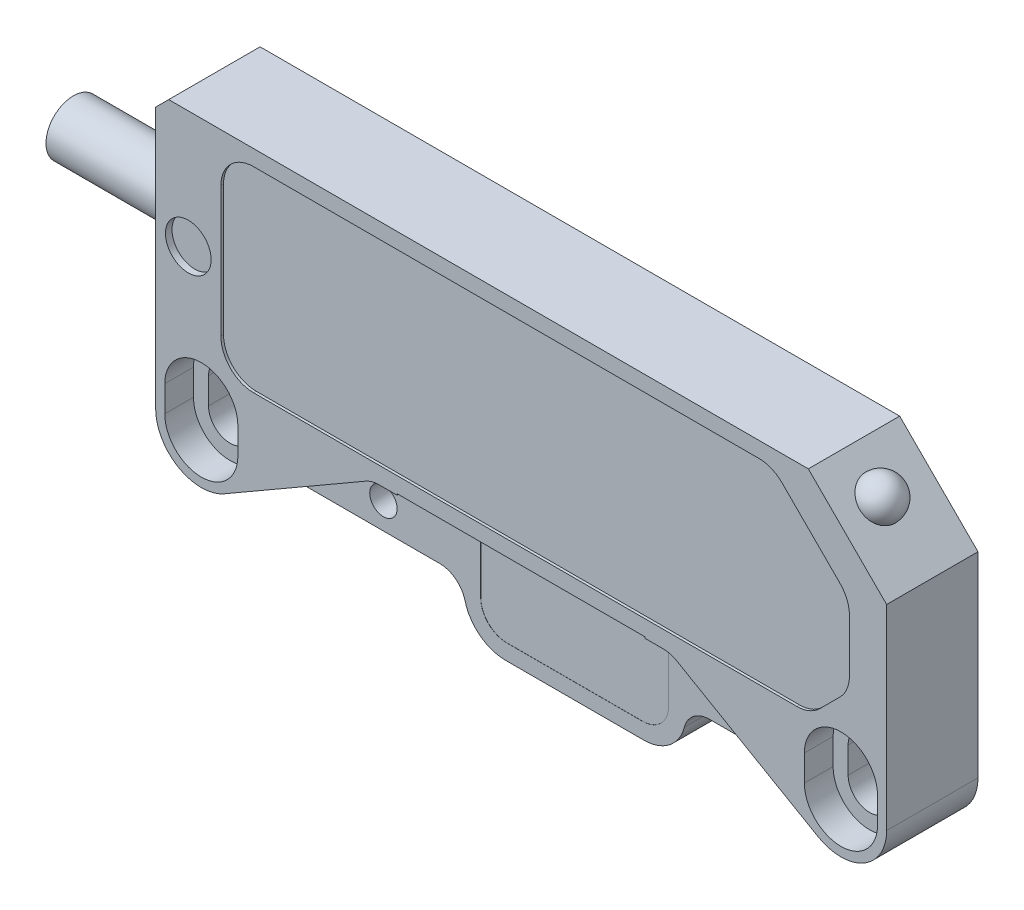
SolidWorks part; units mm, degrees
material "Zinc AG40A (Zn-4Al-0.4Mg; Zamak 3), Cast"
ref_plane "Front Plane" through (0, 0, 0) normal (0, 0, 1) x (1, 0, 0)
ref_plane "Top Plane" through (0, 0, 0) normal (0, 1, 0) x (1, 0, 0)
ref_plane "Right Plane" through (0, 0, 0) normal (1, 0, 0) x (0, 0, -1)
sketch "Sketch1" plane through (0, 0, 0) normal (0, 0, 1) x (1, 0, 0)
  line L1 (28, 0) -> (28, -11.4) construction
  line L2 (0, -4) -> (0, 17)
  line L3 (0, 17) -> (56, 17)
  line L4 (56, -4) -> (56, 17)
  line L5 (28, 17) -> (28, 0) construction
  line L7 (-0.3, 0) -> (16.888, 0) construction
  line L8 (3.5, -7.5) -> (19.5, -7.5)
  line L9 (52.5, -7.5) -> (36.5, -7.5)
  line L10 (19.5, -7.5) -> (19.5, -11.4)
  line L11 (19.5, -11.4) -> (36.5, -11.4)
  line L12 (36.5, -7.5) -> (36.5, -11.4)
  arc A0 (3.5, -7.5) -> (0, -4) centre (3.5, -4) cw
  arc A1 (52.5, -7.5) -> (56, -4) centre (52.5, -4) ccw
  dimension "D4" = 3.5
  dimension "D6" = 21
  dimension "D2" = 56
  dimension "D3" = 11.4
  dimension "D5" = 17
  dimension "D7" = 17
extrude "Boss-Extrude1" add sketch "Sketch1" along normal blind 7
sketch "Sketch2" plane through (0, 0, 7) normal (0, 0, 1) x (1, 0, 0)
  line L0 (0, 17) -> (0, -4) construction
  line L1 (5, 15.8) -> (5, 0.8)
  line L2 (5, 15.8) -> (47.25, 15.8)
  line L3 (47.25, 15.8) -> (53.15, 9.9)
  line L4 (5, 0.8) -> (50.15, 0.8)
  line L5 (28, -11.4) -> (28, 15.8) construction
  line L6 (56, 17) -> (0, 17) construction
  line L7 (53.15, 9.9) -> (53.15, 3.8)
  line L8 (19.5, -11.4) -> (36.5, -11.4) construction
  line L9 (53.15, 3.8) -> (50.15, 0.8)
  point P9 (53.15, 0.8)
  dimension "D1" = 45
  dimension "D2" = 15
  dimension "D3" = 5.9
  dimension "D4" = 1.2
  dimension "D5" = 48.15
  dimension "D8" = 3
  dimension "D6" = 5
extrude "Cut-Extrude1" cut sketch "Sketch2" against normal blind 0.2
fillet "Fillet1" radius 2.5 6 edges at (5, 0.8, 6.9) (5, 15.8, 6.9) (53.15, 9.9, 6.9) (47.25, 15.8, 6.9) (50.15, 0.8, 6.9) (53.15, 3.8, 6.9)
chamfer "Chamfer1" distance 6 angle 45 1 edges at (56, 17, 3.5)
sketch "Sketch6" plane through (0, 0, 7) normal (0, 0, 1) x (1, 0, 0)
  line L0 (49.7, -4) -> (49.7, -2)
  line L1 (55.3, -4) -> (55.3, -2)
  line L2 (56, -4) -> (56, 11) construction
  line L4 (50, 17) -> (0, 17) construction
  arc A0 (49.7, -4) -> (55.3, -4) centre (52.5, -4) ccw
  arc A4 (55.3, -2) -> (49.7, -2) centre (52.5, -2) ccw
  dimension "D1" = 5.6
  dimension "D4" = 21
  dimension "D2" = 2
  dimension "D3" = 0.7
extrude "Cut-Extrude4" cut sketch "Sketch6" against normal blind 2.2
ref_plane "Plane1" through (0, 0, 3.5) normal (0, 0, 1) x (1, 0, 0)
sketch "Sketch9" plane through (0, 0, 4.8) normal (0, 0, 1) x (1, 0, 0)
  line L4 (54.15, -4) -> (54.15, -2)
  line L5 (50.85, -2) -> (50.85, -4)
  line L6 (54.15, -4) -> (54.15, -2)
  line L7 (50.85, -2) -> (50.85, -4)
  arc A4 (50.85, -4) -> (54.15, -4) centre (52.5, -4) ccw
  arc A5 (54.15, -2) -> (50.85, -2) centre (52.5, -2) ccw
  arc A6 (50.85, -4) -> (54.15, -4) centre (52.5, -4) ccw
  arc A7 (54.15, -2) -> (50.85, -2) centre (52.5, -2) ccw
  dimension "D1" = 1.15
extrude "Cut-Extrude5" cut sketch "Sketch9" against normal through all
mirror "Mirror1" about plane through (0, 0, 3.5) normal (0, 0, 1) of "Cut-Extrude4"
sketch "Sketch14" plane through (0, 24, 0) normal (1, 0, 0) x (0, -1, 0)
  line L0 (7, -7) -> (7, 0) construction
  line L2 (7, 0) -> (28, 0) construction
  circle A0 centre (16, -3.5) radius 2.2
  dimension "D1" = 4.4
  dimension "D2" = 9
  dimension "D3" = 3.5
extrude "Cut-Extrude9" cut sketch "Sketch14" along normal blind 0.2
sketch "Sketch19" plane through (0, 0, 7) normal (0, 0, 1) x (1, 0, 0)
  line L0 (19.5, -11.4) -> (36.5, -11.4) construction
  line L1 (20.8, -0.4) -> (35.2, -0.4)
  line L2 (20.8, -0.4) -> (20.8, -8.2)
  line L3 (22.8, -10.2) -> (33.2, -10.2)
  line L4 (35.2, -0.4) -> (35.2, -8.2)
  line L5 (28, -11.4) -> (28, 20.6935) construction
  arc A1 (20.8, -8.2) -> (22.8, -10.2) centre (22.8, -8.2) ccw
  arc A2 (33.2, -10.2) -> (35.2, -8.2) centre (33.2, -8.2) ccw
  dimension "D2" = 9.8
  dimension "D4" = 2
  dimension "D1" = 14.4
  dimension "D3" = 1.2
extrude "Cut-Extrude10" cut sketch "Sketch19" against normal blind 4.11
chamfer "Chamfer3" distance 1 angle 45 1 edges at (0, 17, 3.5)
fillet "Fillet3" radius 3.2 2 edges at (36.5, -11.4, 3.5) (19.5, -11.4, 3.5)
sketch "Sketch28" plane through (0, 0, 7) normal (0, 0, 1) x (1, 0, 0)
  line L0 (16.0981, -0.7679) -> (5.25, -7.0311)
  line L1 (0, 16) -> (0, -4) construction
  line L2 (3.5, -7.5) -> (16.6824, -7.5)
  line L3 (28, -15.8188) -> (28, 23.915) construction
  line L4 (17.6824, -8.5) -> (17.6824, -14.5773)
  line L5 (17.6824, -14.5773) -> (38.3176, -14.5773)
  line L6 (3.5, -7.5) -> (19.5, -7.5) construction
  line L7 (17.0981, -0.5) -> (18.5, -0.5)
  line L8 (18.5, -0.4) -> (37.5, -0.4)
  line L9 (37.5, -0.5) -> (37.5, -0.4)
  line L10 (38.9019, -0.5) -> (37.5, -0.5)
  line L11 (38.3176, -8.5) -> (38.3176, -14.5773)
  line L12 (18.5, -0.5) -> (18.5, -0.4)
  line L13 (52.5, -7.5) -> (39.3176, -7.5)
  line L14 (39.9019, -0.7679) -> (50.75, -7.0311)
  arc A0 (5.25, -7.0311) -> (3.5, -7.5) centre (3.5, -4) cw
  arc A1 (16.0981, -0.7679) -> (17.0981, -0.5) centre (17.0981, -2.5) cw
  arc A2 (38.3176, -8.5) -> (39.3176, -7.5) centre (39.3176, -8.5) cw
  arc A3 (0, -4) -> (3.5, -7.5) centre (3.5, -4) ccw construction
  arc A4 (39.9019, -0.7679) -> (38.9019, -0.5) centre (38.9019, -2.5) ccw
  arc A5 (50.75, -7.0311) -> (52.5, -7.5) centre (52.5, -4) ccw
  arc A6 (17.6824, -8.5) -> (16.6824, -7.5) centre (16.6824, -8.5) ccw
  point P30 (28, -0.4)
  point P33 (17.6824, -7.5)
  point P34 (38.3176, -7.5)
  point P37 (28, -14.5773)
  dimension "D1" = 2
  dimension "D5" = 7
  dimension "D2" = 30
  dimension "D3" = 28
  dimension "D4" = 9.5
  dimension "D6" = 0.1
sketch "Sketch29" plane through (0, 0, 0) normal (0, 0, -1) x (-1, 0, 0)
  line L0 (-28, -19.7391) -> (-28, 26.5422) construction
  line L1 (-50, 17) -> (-1, 17) construction
  line L4 (-22.7, -11.4) -> (-33.3, -11.4) construction
  circle A0 centre (-42.65, -5.5) radius 1.05
  circle A1 centre (-41, -2.7) radius 1.05
  circle A2 centre (-13.35, -5.5) radius 1.05
  circle A3 centre (-15, -2.7) radius 1.05
  point P7 (-41, -2.7)
  point P12 (-28, -11.4)
  dimension "D1" = 29.3
  dimension "D5" = 2.1
  dimension "D4" = 2.1
  dimension "D6" = 22.5
  dimension "D7" = 14.65
  dimension "D2" = 13
  dimension "D3" = 19.7
extrude "Cut-Extrude16" cut sketch "Sketch29" against normal blind 10
ref_plane "Plane2" through (28, 0, 0) normal (-1, 0, 0) x (0, 0, 1)
fillet "Fillet5" radius 2 4 edges at (19.5, -7.85, 0) (19.5, -7.5, 3.5) (19.5, -8.2, 3.5) (19.5, -7.85, 7)
fillet "Fillet6" radius 2 4 edges at (36.5, -7.5, 3.5) (36.5, -7.85, 0) (36.5, -7.85, 7) (36.5, -8.2, 3.5)
mirror "Mirror2" about plane through (28, 0, 0) normal (-1, 0, 0) of "Mirror1", "Cut-Extrude4", "Cut-Extrude5"
sketch "Sketch31" plane through (0, 0, 7) normal (0, 0, 1) x (1, 0, 0)
  line L1 (0, 16) -> (0, -4) construction
  line L2 (50, 17) -> (1, 17) construction
  circle A0 centre (2.5, 8) radius 1.75
  dimension "D1" = 3.5
  dimension "D2" = 2.5
  dimension "D3" = 9
extrude "Cut-Extrude17" cut sketch "Sketch31" against normal blind 0.5
ref_plane "Plane3" through (28, 0, 0) normal (1, 0, 0) x (0, 0, -1)
extrude "Cut-Extrude19" cut sketch "Sketch28" against normal blind 4.1
ref_plane "Plane4" through (0, 0, 3.8) normal (0, 0, -1) x (-1, 0, 0)
sketch "Sketch32" plane through (0, 0, 3.8) normal (0, 0, -1) x (-1, 0, 0)
  line L0 (-56, 11) -> (-50, 17) construction
  line L1 (-52.3335, 14.6665) -> (-54.5962, 16.9293) construction
  line L2 (-52.3335, 14.6665) -> (-53.4648, 13.5352)
  line L3 (-52.3335, 14.6665) -> (-53.4648, 15.7979)
  arc A0 (-53.4648, 15.7979) -> (-53.4648, 13.5352) centre (-52.3335, 14.6665) ccw
  dimension "D2" = 1.6
  dimension "D1" = 3.3
revolve "Revolve1" add sketch "Sketch32" angle 360 about L1
sketch "Sketch33" plane through (0.2, 0, 0) normal (-1, 0, 0) x (0, 0, 1)
  circle A0 centre (3.5, 8) radius 2.1
  dimension "D1" = 4.2
extrude "Boss-Extrude2" add sketch "Sketch33" along normal blind 10
